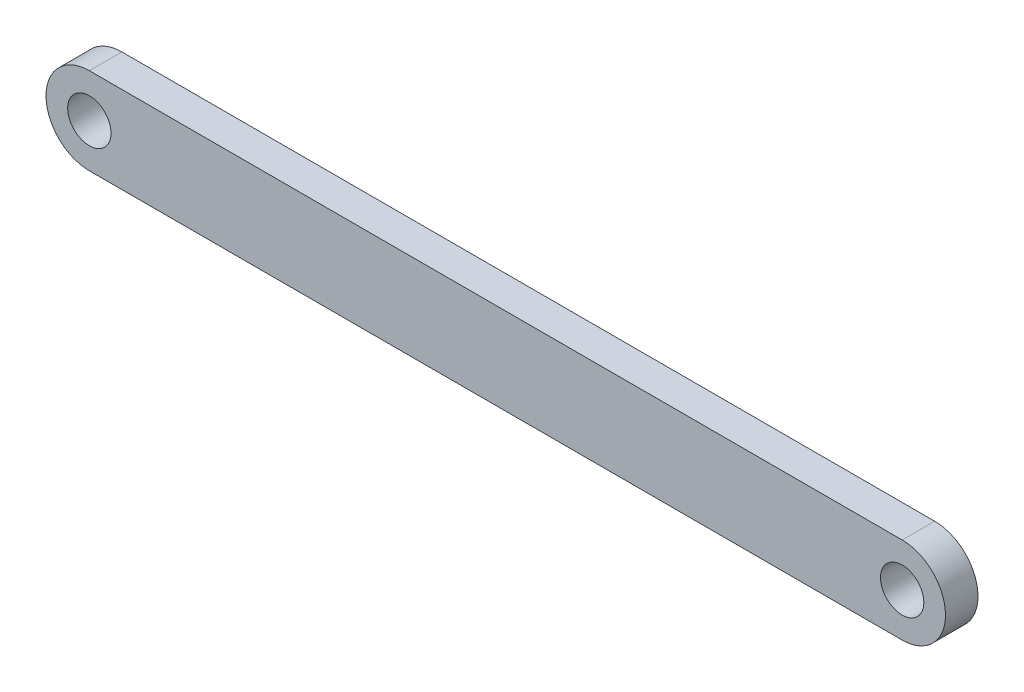
SolidWorks part; units mm, degrees
ref_plane "Front Plane" through (0, 0, 0) normal (0, 0, 1) x (1, 0, 0)
ref_plane "Top Plane" through (0, 0, 0) normal (0, 1, 0) x (1, 0, 0)
ref_plane "Right Plane" through (0, 0, 0) normal (1, 0, 0) x (0, 0, -1)
sketch "Sketch1" plane through (0, 34.7031, 0) normal (0, 0, 1) x (1, 0, 0)
  line L1 (-30.3724, 17.4326) -> (44.6276, 17.4326)
  line L3 (-30.3724, 9.4326) -> (44.6276, 9.4326)
  arc A0 (-30.3724, 17.4326) -> (-30.3724, 9.4326) centre (-30.3724, 13.4326) ccw
  arc A1 (44.6276, 17.4326) -> (44.6276, 9.4326) centre (44.6276, 13.4326) cw
  circle A2 centre (-30.3724, 13.4326) radius 2
  circle A3 centre (44.6276, 13.4326) radius 2
  dimension "D3" = 4
  dimension "D4" = 4
  dimension "D1" = 75
  dimension "D2" = 8
extrude "Boss-Extrude1" add sketch "Sketch1" along normal blind 3
